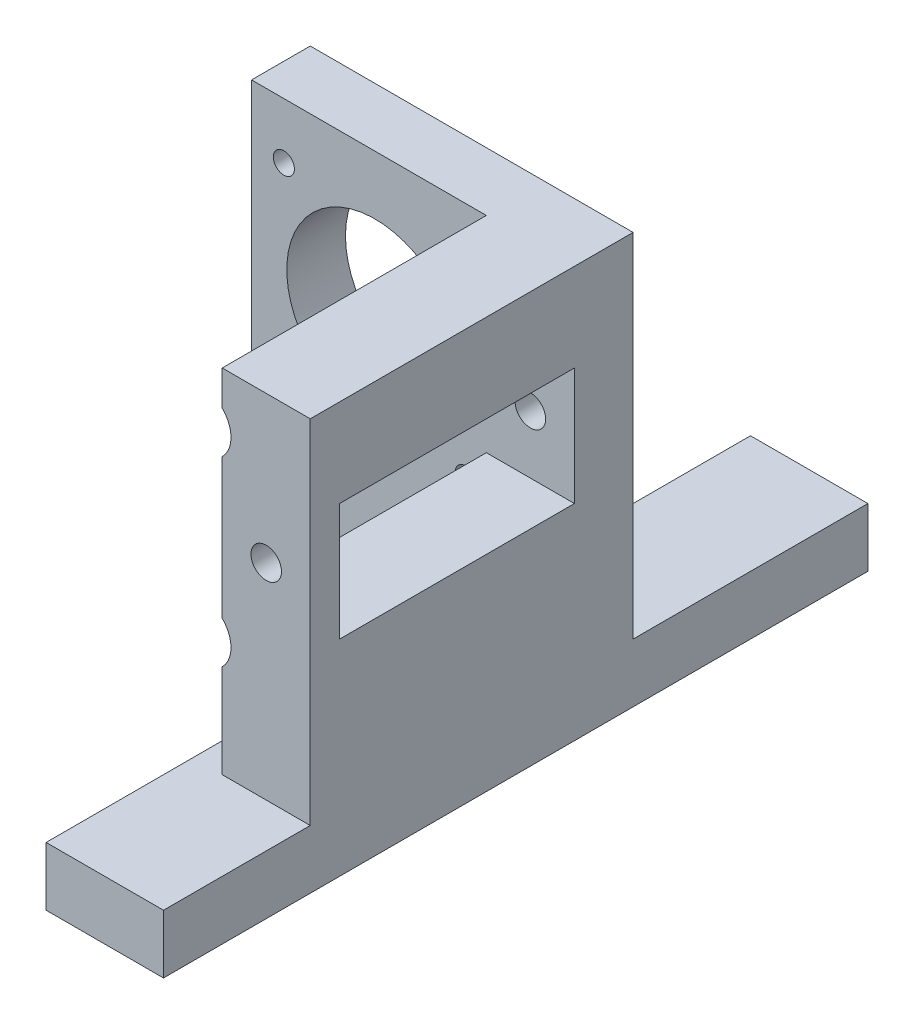
SolidWorks part; units mm, degrees
ref_plane "Front Plane" through (0, 0, 0) normal (0, 0, 1) x (1, 0, 0)
ref_plane "Top Plane" through (0, 0, 0) normal (0, 1, 0) x (1, 0, 0)
ref_plane "Right Plane" through (0, 0, 0) normal (1, 0, 0) x (0, 0, -1)
sketch "Sketch4" plane through (0, 0, 0) normal (0, 1, 0) x (1, 0, 0)
  line L1 (0, 0) -> (40, 0)
  line L2 (0, 0) -> (0, 80)
  line L3 (0, 80) -> (40, 80)
  line L4 (40, 0) -> (40, 80)
  dimension "D1" = 80
  dimension "D2" = 40
extrude "Boss-Extrude4" add sketch "Sketch4" along normal blind 5
sketch "Sketch5" plane through (0, 5, 0) normal (0, 1, 0) x (1, 0, 0)
  line L0 (40, 40) -> (30, 40)
  line L1 (30, 30) -> (30, 50) construction
  line L2 (40, 50) -> (30, 50)
  line L3 (30, 50) -> (30, 55)
  line L4 (0, 80) -> (0, 0)
  line L5 (0, 0) -> (40, 0)
  line L6 (40, 0) -> (40, 80)
  line L7 (40, 80) -> (0, 80)
  line L8 (0, 80) -> (0, 0)
  line L9 (0, 0) -> (40, 0)
  line L10 (40, 0) -> (40, 80)
  line L11 (40, 80) -> (0, 80)
  line L12 (30, 55) -> (40, 55)
  line L13 (40, 55) -> (40, 50)
  line L14 (40, 30) -> (30, 30)
  line L15 (30, 30) -> (30, 25)
  line L16 (30, 25) -> (40, 25)
  line L17 (40, 25) -> (40, 30)
  point P9 (30, 40)
  line M11 (40, 0) -> (40, 80)
  dimension "D2" = 10
  dimension "D3" = 10
  dimension "D4" = 5
  dimension "D5" = 5
  dimension "D1" = 0
extrude "Boss-Extrude6" add sketch "Sketch5" along normal blind 50 contours L12 L3 L2 M11 | L15 L16 L10 L14 region at (35, 5, -52.5) region at (35, 5, -27.5)
sketch "Sketch7" plane through (0, 0, -50) normal (0, 0, 1) x (1, 0, 0)
  line L1 (30, 5) -> (40, 5)
  line L2 (30, 5) -> (30, 30)
  line L3 (30, 30) -> (40, 30)
  line L4 (40, 5) -> (40, 30)
  line L5 (40, 55) -> (40, 5) construction
  line L7 (30, 55) -> (40, 55)
  line L8 (30, 55) -> (30, 50)
  line L9 (30, 50) -> (40, 50)
  line L10 (40, 55) -> (40, 50)
  dimension "D1" = 25
  dimension "D2" = 10
  dimension "D3" = 5
extrude "Boss-Extrude7" add sketch "Sketch7" along normal up to surface (20 mm away) contours L8 L7 L10 L9 | L2 L1 L4 L3 up to face at (35, 30, -30)
sketch "Sketch8" plane through (0, 0, -80) normal (0, 0, -1) x (-1, 0, 0)
  line L4 (-40, 0) -> (0, 0)
  line L5 (0, 0) -> (0, 5)
  line L6 (0, 5) -> (-40, 5)
  line L7 (-40, 5) -> (-40, 0)
  line L8 (-40, 0) -> (0, 0)
  line L9 (0, 0) -> (0, 5)
  line L10 (0, 5) -> (-40, 5)
  line L11 (-40, 5) -> (-40, 0)
  dimension "D1" = 0
extrude "Boss-Extrude8" add sketch "Sketch8" along normal blind 20 contours L8 L9 L10 L11
sketch "Sketch9" plane through (0, 0, 0) normal (-1, 0, 0) x (0, 0, 1)
  line L4 (-100, 0) -> (0, 0)
  line L5 (0, 0) -> (0, 5)
  line L6 (0, 5) -> (-100, 5)
  line L7 (-100, 5) -> (-100, 0)
  line L8 (-100, 0) -> (0, 0)
  line L9 (0, 0) -> (0, 5)
  line L10 (0, 5) -> (-100, 5)
  line L11 (-100, 5) -> (-100, 0)
  dimension "D1" = 0
extrude "Boss-Extrude9" add sketch "Sketch9" along normal blind 10
sketch "Sketch10" plane through (30, 0, 0) normal (-1, 0, 0) x (0, 0, 1)
  line L0 (-25, 5) -> (-55, 5) construction
  line L1 (-55, 55) -> (-50, 55)
  line L2 (-55, 55) -> (-55, 5)
  line L3 (-55, 5) -> (-50, 5)
  line L4 (-50, 55) -> (-50, 5)
  dimension "D1" = 5
extrude "Boss-Extrude10" add sketch "Sketch10" along normal blind 40 contours L2 L1 L4 L3
sketch "Sketch11" plane through (0, 55, 0) normal (0, 1, 0) x (1, 0, 0)
  line L6 (40, 55) -> (-10, 55)
  line L7 (-10, 55) -> (-10, 50)
  line L8 (-10, 50) -> (30, 50)
  line L9 (30, 50) -> (30, 25)
  line L10 (30, 25) -> (40, 25)
  line L11 (40, 25) -> (40, 55)
  line L12 (40, 55) -> (-10, 55)
  line L13 (-10, 55) -> (-10, 50)
  line L14 (-10, 50) -> (30, 50)
  line L15 (30, 50) -> (30, 25)
  line L16 (30, 25) -> (40, 25)
  line L17 (40, 25) -> (40, 55)
  dimension "D1" = 0
extrude "Boss-Extrude11" add sketch "Sketch11" along normal blind 10
sketch "Sketch12" plane through (0, 0, -50) normal (0, 0, 1) x (1, 0, 0)
  line L0 (30, 50) -> (30, 30)
  line L1 (30, 40) -> (26, 40)
  line L2 (0.3934, 50.6066) -> (-3.227, 54.227)
  line L3 (-10, 61) -> (32, 61)
  line L4 (-10, 61) -> (-10, 19)
  line L5 (-10, 19) -> (32, 19)
  line L6 (32, 61) -> (32, 19)
  line L7 (-10, 61) -> (32, 19) construction
  line L8 (30, 30) -> (40, 30)
  line L9 (40, 30) -> (40, 50)
  line L10 (40, 50) -> (30, 50)
  line L11 (30, 50) -> (30, 65)
  line L12 (30, 65) -> (-10, 65)
  line L13 (-10, 65) -> (-10, 5)
  line L14 (-10, 5) -> (30, 5)
  line L15 (30, 5) -> (30, 30)
  line L16 (30, 30) -> (40, 30)
  line L17 (40, 30) -> (40, 50)
  line L18 (40, 50) -> (30, 50)
  line L19 (30, 50) -> (30, 65)
  line L20 (30, 65) -> (-10, 65)
  line L21 (-10, 65) -> (-10, 5)
  line L22 (-10, 5) -> (30, 5)
  line L23 (30, 5) -> (30, 30)
  line L24 (-10, 19) -> (32, 61) construction
  line L25 (-2.6998, 24.5002) -> (-4.4998, 24.5002) construction
  line L26 (24.6998, 24.5002) -> (-2.6998, 24.5002)
  line L27 (26.4998, 26.3002) -> (26.4998, 53.6998)
  line L28 (24.6998, 55.4998) -> (-2.6998, 55.4998)
  line L29 (-4.4998, 26.3002) -> (-4.4998, 53.6998)
  line L30 (26.4998, 24.5002) -> (-4.4998, 55.4998) construction
  line L31 (26.4998, 55.4998) -> (-4.4998, 24.5002) construction
  line L32 (26.4998, 24.5002) -> (24.6998, 24.5002) construction
  line L33 (26.4998, 24.5002) -> (26.4998, 26.3002) construction
  line L34 (26.4998, 53.6998) -> (26.4998, 55.4998) construction
  line L35 (26.4998, 55.4998) -> (24.6998, 55.4998) construction
  line L36 (11, 40) -> (0.3934, 50.6066) construction
  line L37 (26, 40) -> (11, 40) construction
  line L38 (-3.227, 54.227) -> (-4.4998, 55.4998) construction
  line L39 (-4.4998, 53.6998) -> (-4.4998, 55.4998) construction
  line L40 (-2.6998, 55.4998) -> (-4.4998, 55.4998) construction
  line L41 (-4.4998, 24.5002) -> (-4.4998, 26.3002) construction
  circle A0 centre (11, 40) radius 15
  circle A1 centre (-4.4998, 55.4998) radius 1.8
  circle A2 centre (26.4998, 55.4998) radius 1.8
  circle A3 centre (26.4998, 24.5002) radius 1.8
  circle A4 centre (-4.4998, 24.5002) radius 1.8
  dimension "D2" = 19
  dimension "D3" = 30
  dimension "D6" = 3.6
  dimension "D7" = 3.6
  dimension "D1" = 0
  dimension "D4" = 42
  dimension "D5" = 21.92
extrude "Cut-Extrude1" cut sketch "Sketch12" against normal up to surface (5 mm away) contours A0 | A1 | A2 | A4 | A3 region at (11, 40, -50) region at (-4.4998, 55.4998, -50) up to face at (15, 35, -55)
sketch "Sketch13" plane through (0, 0, -50) normal (0, 0, 1) x (1, 0, 0)
  line L0 (40, 40) -> (35, 40) construction
  line L8 (30, 30) -> (40, 30)
  line L9 (40, 30) -> (40, 50)
  line L10 (40, 50) -> (30, 50)
  line L11 (30, 50) -> (30, 65)
  line L12 (30, 65) -> (-10, 65)
  line L13 (-10, 65) -> (-10, 5)
  line L14 (-10, 5) -> (30, 5)
  line L15 (30, 5) -> (30, 30)
  line L16 (30, 30) -> (40, 30)
  line L17 (40, 30) -> (40, 50)
  line L18 (40, 50) -> (30, 50)
  line L19 (30, 50) -> (30, 65)
  line L20 (30, 65) -> (-10, 65)
  line L21 (-10, 65) -> (-10, 5)
  line L22 (-10, 5) -> (30, 5)
  line L23 (30, 5) -> (30, 30)
  circle A0 centre (35, 40) radius 2.25
  dimension "D3" = 4.5
  dimension "D2" = 5
  dimension "D1" = 0
extrude "Cut-Extrude2" cut sketch "Sketch13" against normal through all both and the other way through all contours A0
sketch "Sketch14" plane through (0, 0, -25) normal (0, 0, 1) x (1, 0, 0)
  circle A0 centre (35, 40) radius 2.25 construction
  circle A1 centre (35, 40) radius 2.25
  circle A2 centre (35, 40) radius 4
  dimension "D1" = 8
extrude "Cut-Extrude4" cut sketch "Sketch14" against normal blind 2 contours A1 | A2
sketch "Sketch15" plane through (0, 0, -55) normal (0, 0, -1) x (-1, 0, 0)
  circle A0 centre (-35, 40) radius 2.25 construction
  circle A1 centre (-35, 40) radius 2.25
  circle A2 centre (-35, 40) radius 4
  dimension "D1" = 8
extrude "Cut-Extrude5" cut sketch "Sketch15" against normal blind 2
sketch "Sketch17" plane through (0, 0, -25) normal (0, 0, 1) x (1, 0, 0)
  line L0 (26.4998, 55.4998) -> (26.4998, 24.5002)
  circle A0 centre (26.4998, 55.4998) radius 1.8 construction
  circle A1 centre (26.4998, 55.4998) radius 1.8
  circle A2 centre (26.4998, 55.4998) radius 5
  circle A3 centre (26.4998, 24.5002) radius 5
  line M4 (30, 65) -> (30, 5)
  dimension "D1" = 10
  dimension "D2" = 10
extrude "Cut-Extrude6" cut sketch "Sketch17" against normal up to surface (25 mm away) contours A2 A1 M4 | A3 M4 | A3 M4 | A2 M4 region at (21.9924, 57.3406, -25) region at (26.0733, 24.5002, -25) region at (30.6084, 55.4998, -25) region at (30.6084, 24.5002, -25) up to face at (37.25, 40, -50)
sketch "Sketch19" plane through (0, 0, -55) normal (0, 0, -1) x (-1, 0, 0)
  line L4 (10, 5) -> (10, 65)
  line L5 (10, 65) -> (-40, 65)
  line L6 (-40, 65) -> (-40, 5)
  line L7 (-40, 5) -> (10, 5)
  line L8 (10, 5) -> (10, 65)
  line L9 (10, 65) -> (-40, 65)
  line L10 (-40, 65) -> (-40, 5)
  line L11 (-40, 5) -> (10, 5)
  circle A0 centre (4.4998, 55.4998) radius 1.8 construction
  circle A1 centre (4.4998, 24.5002) radius 1.8 construction
  circle A2 centre (-26.4998, 24.5002) radius 1.8 construction
  circle A3 centre (-11, 40) radius 15 construction
  circle A4 centre (-35, 40) radius 4 construction
  circle A6 centre (-26.4998, 55.4998) radius 1.8 construction
  circle A7 centre (4.4998, 55.4998) radius 1.8
  circle A8 centre (4.4998, 24.5002) radius 1.8
  circle A9 centre (-26.4998, 24.5002) radius 1.8
  circle A10 centre (-11, 40) radius 15
  circle A11 centre (-35, 40) radius 4
  circle A13 centre (-26.4998, 55.4998) radius 1.8
  dimension "D1" = 0
extrude "Boss-Extrude13" add sketch "Sketch19" along normal blind 5
sketch "Sketch20" plane through (0, 0, -53) normal (0, 0, -1) x (-1, 0, 0)
  circle A0 centre (-35, 40) radius 2.25 construction
  circle A1 centre (-35, 40) radius 4
  circle A2 centre (-35, 40) radius 4
  circle A3 centre (-35, 40) radius 2.25
  dimension "D1" = 0
extrude "Boss-Extrude14" add sketch "Sketch20" along normal blind 5
sketch "Sketch21" plane through (40, 0, 0) normal (1, 0, 0) x (0, 0, -1)
  line L0 (50, 50) -> (50, 30) construction
  line L1 (30, 50) -> (30, 30) construction
  line L2 (30, 50) -> (50, 50) construction
  line L3 (30, 30) -> (50, 30) construction
  line L4 (50, 50) -> (50, 30)
  line L5 (30, 50) -> (30, 30)
  line L6 (30, 50) -> (50, 50)
  line L7 (30, 30) -> (50, 30)
  line L8 (100, 5) -> (60, 5)
  line L9 (60, 5) -> (60, 65)
  line L10 (60, 65) -> (25, 65)
  line L11 (25, 65) -> (25, 5)
  line L12 (25, 5) -> (0, 5)
  line L13 (0, 5) -> (0, 0)
  line L14 (0, 0) -> (100, 0)
  line L15 (100, 0) -> (100, 5)
  line L16 (100, 5) -> (60, 5)
  line L17 (60, 5) -> (60, 65)
  line L18 (60, 65) -> (25, 65)
  line L19 (25, 65) -> (25, 5)
  line L20 (25, 5) -> (0, 5)
  line L21 (0, 5) -> (0, 0)
  line L22 (0, 0) -> (100, 0)
  line L23 (100, 0) -> (100, 5)
  dimension "D1" = 0
extrude "Boss-Extrude15" add sketch "Sketch21" along normal blind 5
sketch "Sketch22" plane through (0, 0, -60) normal (0, 0, -1) x (-1, 0, 0)
  circle A0 centre (-35, 40) radius 4 construction
  circle A1 centre (-35, 40) radius 4
extrude "Boss-Extrude16" add sketch "Sketch22" against normal up to surface (10 mm away) up to face at (26.0833, 38.3333, -50)
sketch "Sketch23" plane through (0, 0, -25) normal (0, 0, 1) x (1, 0, 0)
  circle A0 centre (35, 40) radius 4 construction
  circle A1 centre (35, 40) radius 4
extrude "Boss-Extrude17" add sketch "Sketch23" against normal up to surface (5 mm away) up to face at (37.25, 40, -30)
sketch "Sketch24" plane through (0, 0, -30) normal (0, 0, -1) x (-1, 0, 0)
  line L0 (-30, 30) -> (-45, 50) construction
  line L1 (-30, 50) -> (-45, 30) construction
  line L4 (-30, 50) -> (-45, 50)
  line L5 (-45, 50) -> (-45, 30)
  line L6 (-45, 30) -> (-30, 30)
  line L7 (-30, 30) -> (-30, 50)
  line L8 (-30, 50) -> (-45, 50)
  line L9 (-45, 50) -> (-45, 30)
  line L10 (-45, 30) -> (-30, 30)
  line L11 (-30, 30) -> (-30, 50)
  circle A0 centre (-37.5, 40) radius 2.6
  dimension "D2" = 5.2
  dimension "D1" = 0
extrude "Cut-Extrude7" cut sketch "Sketch24" against normal through all both and the other way through all contours A0
sketch "Sketch25" plane through (0, 0, 0) normal (0, -1, 0) x (1, 0, 0)
  line L4 (45, 0) -> (-10, 0)
  line L5 (-10, 0) -> (-10, -100)
  line L6 (-10, -100) -> (45, -100)
  line L7 (45, -100) -> (45, 0)
  line L8 (45, 0) -> (-10, 0)
  line L9 (-10, 0) -> (-10, -100)
  line L10 (-10, -100) -> (45, -100)
  line L11 (45, -100) -> (45, 0)
  dimension "D1" = 0
extrude "Boss-Extrude18" add sketch "Sketch25" along normal blind 5
sketch "Sketch26" plane through (0, 0, 0) normal (0, 0, 1) x (1, 0, 0)
  line L4 (-10, 5) -> (-10, -5)
  line L5 (-10, -5) -> (45, -5)
  line L6 (45, -5) -> (45, 5)
  line L7 (45, 5) -> (-10, 5)
  line L8 (-10, 5) -> (-10, -5)
  line L9 (-10, -5) -> (45, -5)
  line L10 (45, -5) -> (45, 5)
  line L11 (45, 5) -> (-10, 5)
  dimension "D1" = 0
extrude "Boss-Extrude19" add sketch "Sketch26" along normal blind 20
sketch "Sketch27" plane through (30, 0, 0) normal (-1, 0, 0) x (0, 0, 1)
  line L1 (-30, 50) -> (-25, 50)
  line L2 (-30, 50) -> (-30, 30)
  line L3 (-30, 30) -> (-25, 30)
  line L4 (-25, 50) -> (-25, 30)
  line L5 (-25, 51.9293) -> (-25, 28.0707) construction
  dimension "D1" = 5
  dimension "D2" = 20
extrude "Cut-Extrude8" cut sketch "Sketch27" against normal blind 15
sketch "Sketch28" plane through (0, 0, -25) normal (0, 0, 1) x (1, 0, 0)
  line L5 (45, 5) -> (45, 30)
  line L6 (45, 30) -> (30, 30)
  line L7 (30, 30) -> (30, 28.0707)
  line L8 (30, 20.9297) -> (30, 5)
  line L9 (30, 5) -> (45, 5)
  line L10 (45, 5) -> (45, 30)
  line L11 (45, 30) -> (30, 30)
  line L12 (30, 30) -> (30, 28.0707)
  line L13 (30, 20.9297) -> (30, 5)
  line L14 (30, 5) -> (45, 5)
  line L15 (30, 51.9293) -> (30, 50)
  line L16 (30, 50) -> (45, 50)
  line L17 (45, 50) -> (45, 65)
  line L18 (45, 65) -> (30, 65)
  line L19 (30, 65) -> (30, 59.0703)
  line L20 (30, 51.9293) -> (30, 50)
  line L21 (30, 50) -> (45, 50)
  line L22 (45, 50) -> (45, 65)
  line L23 (45, 65) -> (30, 65)
  line L24 (30, 65) -> (30, 59.0703)
  arc A1 (30, 20.9297) -> (30, 28.0707) centre (26.4998, 24.5002) ccw
  arc A2 (30, 20.9297) -> (30, 28.0707) centre (26.4998, 24.5002) ccw
  arc A3 (30, 51.9293) -> (30, 59.0703) centre (26.4998, 55.4998) ccw
  arc A4 (30, 51.9293) -> (30, 59.0703) centre (26.4998, 55.4998) ccw
  dimension "D1" = 0
  dimension "D2" = 0
extrude "Boss-Extrude20" add sketch "Sketch28" along normal blind 20
sketch "Sketch29" plane through (0, 30, 0) normal (0, 1, 0) x (1, 0, 0)
  line L7 (30, 5) -> (45, 5)
  line L8 (30, 5) -> (30, 10)
  line L9 (30, 10) -> (45, 10)
  line L10 (45, 5) -> (45, 10)
  line L11 (45, 5) -> (45, 50) construction
  dimension "D1" = 5
  dimension "D2" = 15
extrude "Boss-Extrude21" add sketch "Sketch29" along normal blind 20
sketch "Sketch30" plane through (0, 0, -60) normal (0, 0, -1) x (-1, 0, 0)
  circle A0 centre (-37.5, 40) radius 2.6 construction
  circle A1 centre (-37.5, 40) radius 2.6
extrude "Cut-Extrude9" cut sketch "Sketch30" against normal blind 60
sketch "Sketch31" plane through (0, 5, 0) normal (0, 1, 0) x (1, 0, 0)
  line L0 (25, -20) -> (25, 50)
  line L1 (25, -400) -> (25, 100) construction
  line L2 (25, 60) -> (25, 100)
  line L4 (-10, 100) -> (-10, 60)
  line L5 (-10, 60) -> (45, 60)
  line L6 (45, 60) -> (45, 100)
  line L7 (45, 100) -> (-10, 100)
  line L8 (-10, 100) -> (-10, 60)
  line L9 (-10, 60) -> (25, 60)
  line L11 (25, 100) -> (-10, 100)
  line L14 (45, 5) -> (30, 5)
  line L15 (30, 5) -> (30, 50)
  line L16 (30, 50) -> (-10, 50)
  line L17 (-10, 50) -> (-10, -20)
  line L18 (-10, -20) -> (45, -20)
  line L19 (45, -20) -> (45, 5)
  line L22 (25, 50) -> (-10, 50)
  line L23 (-10, 50) -> (-10, -20)
  line L24 (-10, -20) -> (25, -20)
  dimension "D3" = 35
  dimension "D1" = 0
  dimension "D2" = 0
extrude "Cut-Extrude10" cut sketch "Sketch31" against normal blind 10
